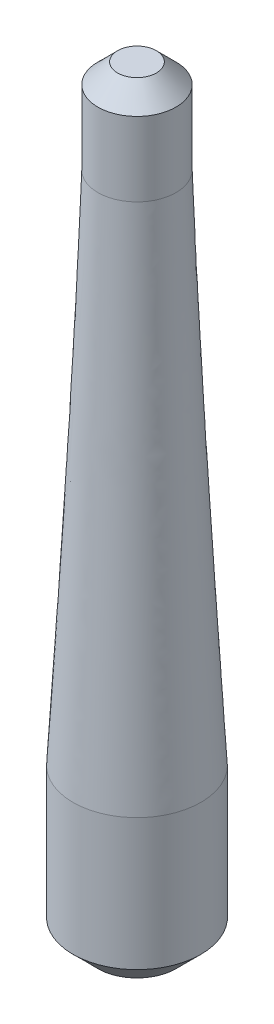
SolidWorks part; units mm, degrees
ref_plane "Front Plane" through (0, 0, 0) normal (0, 0, 1) x (1, 0, 0)
ref_plane "Top Plane" through (0, 0, 0) normal (0, 1, 0) x (1, 0, 0)
ref_plane "Right Plane" through (0, 0, 0) normal (1, 0, 0) x (0, 0, -1)
sketch "Sketch1" plane through (0, 0, 0) normal (0, 1, 0) x (1, 0, 0)
  circle A0 centre (0, 0) radius 2.6
  dimension "D1" = 5.2
ref_plane "Plane1" through (0, 20.955, 0) normal (0, 1, 0) x (1, 0, 0)
sketch "Sketch2" plane through (0, 20.955, 0) normal (0, 1, 0) x (1, 0, 0)
  circle A0 centre (0, 0) radius 1.5875
  dimension "D1" = 3.175
loft "Loft1" add profiles "Sketch2", "Sketch1" connector at (-0.3774, 20.955, 1.542) connector at (-1.7595, 0, 1.9142)
sketch "Sketch3" plane through (0, 0, 0) normal (0, -1, 0) x (1, 0, 0)
  circle A1 centre (0, 0) radius 2.6
  circle A2 centre (0, 0) radius 2.6
  dimension "D1" = 0
extrude "Boss-Extrude1" add sketch "Sketch3" along normal blind 6.35
sketch "Sketch4" plane through (0, 20.955, 0) normal (0, 1, 0) x (1, 0, 0)
  circle A1 centre (0, 0) radius 1.5875
  circle A2 centre (0, 0) radius 1.5875
  dimension "D1" = 0
extrude "Boss-Extrude2" add sketch "Sketch4" along normal blind 3.81
chamfer "Chamfer5" distance 1 1 edges at (0, -6.35, -2.6)
chamfer "Chamfer6" distance 0.8 angle 45 1 edges at (0, 24.765, 1.5875)
